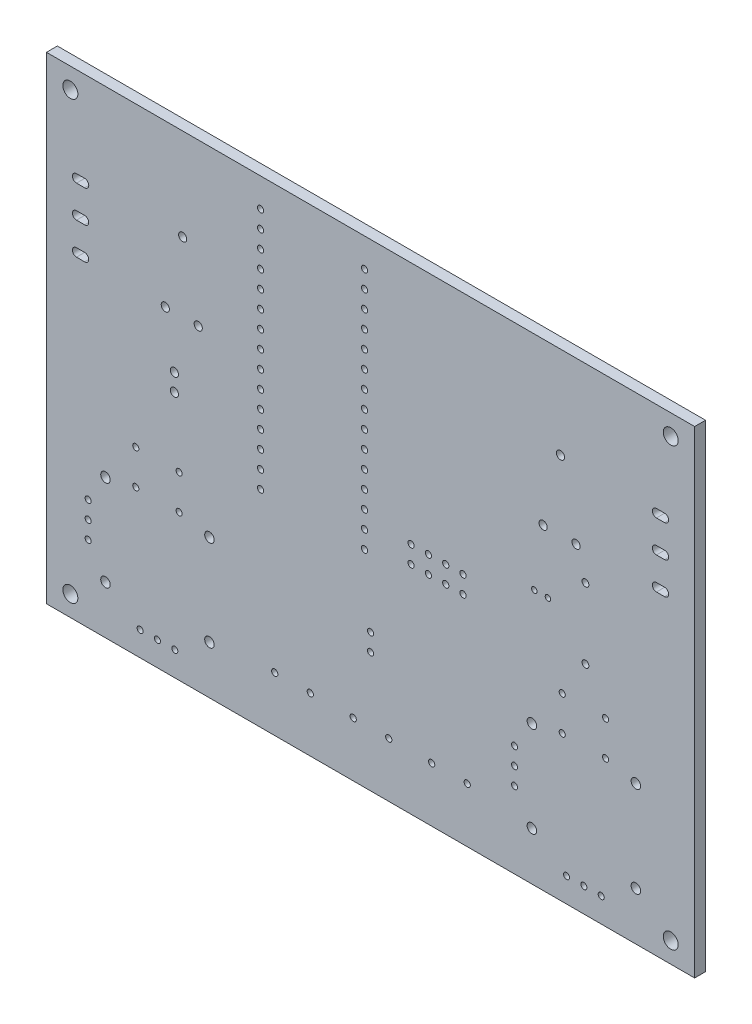
SolidWorks part; units mm, degrees
material "Copper"
ref_plane "Front" through (0, 0, 0) normal (0, 0, 1) x (1, 0, 0)
ref_plane "Top" through (0, 0, 0) normal (0, 1, 0) x (1, 0, 0)
ref_plane "Right" through (0, 0, 0) normal (1, 0, 0) x (0, 0, -1)
sketch "Sketch1" plane through (0, 0, 0) normal (0, 0, 1) x (1, 0, 0)
  line B0 (0, 70) -> (0, 0)
  circle B1 centre (19.9601, 56.5399) radius 1.08
  circle B2 centre (31.38, 60.7) radius 0.4572
  circle B3 centre (31.3799, 60.6999) radius 0.762
  circle B4 centre (31.38, 58.16) radius 0.4572
  circle B5 centre (17.42, 46.38) radius 0.6
  circle B6 centre (17.4201, 46.3799) radius 1.08
  line B7 (95, 70) -> (0, 70)
  line B8 (0, 0) -> (95, 0)
  line B9 (95, 0) -> (95, 70)
  line B10 (6, 57.2) -> (4, 57.2)
  line B11 (4, 57.2) -> (6, 57.2)
  line B12 (6, 55.2) -> (4, 55.2)
  line B13 (4, 55.2) -> (6, 55.2)
  line B14 (5.6, 56.8) -> (4.4, 56.8)
  line B15 (4.4, 56.8) -> (5.6, 56.8)
  line B16 (5.6, 55.6) -> (4.4, 55.6)
  line B17 (4.4, 55.6) -> (5.6, 55.6)
  line B18 (6, 52.5) -> (4, 52.5)
  line B19 (4, 52.5) -> (6, 52.5)
  line B20 (6, 50.5) -> (4, 50.5)
  line B21 (4, 50.5) -> (6, 50.5)
  line B22 (5.6, 52.1) -> (4.4, 52.1)
  line B23 (4.4, 52.1) -> (5.6, 52.1)
  line B24 (5.6, 50.9) -> (4.4, 50.9)
  line B25 (4.4, 50.9) -> (5.6, 50.9)
  line B26 (6, 47.8) -> (4, 47.8)
  line B27 (4, 47.8) -> (6, 47.8)
  line B28 (6, 45.8) -> (4, 45.8)
  line B29 (4, 45.8) -> (6, 45.8)
  line B30 (5.6, 47.4) -> (4.4, 47.4)
  line B31 (4.4, 47.4) -> (5.6, 47.4)
  line B32 (5.6, 46.2) -> (4.4, 46.2)
  line B33 (4.4, 46.2) -> (5.6, 46.2)
  line B34 (91.0001, 57.2) -> (89.0001, 57.2)
  line B35 (89.0001, 57.2) -> (91.0001, 57.2)
  line B36 (91.0001, 55.2) -> (89.0001, 55.2)
  line B37 (89.0001, 55.2) -> (91.0001, 55.2)
  line B38 (90.6, 56.8) -> (89.4, 56.8)
  line B39 (89.4, 56.8) -> (90.6, 56.8)
  line B40 (90.6, 55.6) -> (89.4, 55.6)
  line B41 (89.4, 55.6) -> (90.6, 55.6)
  line B42 (91.0001, 52.5) -> (89.0001, 52.5)
  line B43 (89.0001, 52.5) -> (91.0001, 52.5)
  line B44 (91.0001, 50.5) -> (89.0001, 50.5)
  line B45 (89.0001, 50.5) -> (91.0001, 50.5)
  line B46 (90.6, 52.1) -> (89.4, 52.1)
  line B47 (89.4, 52.1) -> (90.6, 52.1)
  line B48 (90.6, 50.9) -> (89.4, 50.9)
  line B49 (89.4, 50.9) -> (90.6, 50.9)
  line B50 (91.0001, 47.8) -> (89.0001, 47.8)
  line B51 (89.0001, 47.8) -> (91.0001, 47.8)
  line B52 (91.0001, 45.8) -> (89.0001, 45.8)
  line B53 (89.0001, 45.8) -> (91.0001, 45.8)
  line B54 (90.6, 47.4) -> (89.4, 47.4)
  line B55 (89.4, 47.4) -> (90.6, 47.4)
  line B56 (90.6, 46.2) -> (89.4, 46.2)
  line B57 (89.4, 46.2) -> (90.6, 46.2)
  line B58 (19.65, 39.67) -> (19.65, 37.87)
  line B59 (19.65, 37.87) -> (17.85, 37.87)
  line B60 (17.85, 37.87) -> (17.85, 39.67)
  line B61 (17.85, 39.67) -> (19.65, 39.67)
  line B62 (52.6907, 32.4793) -> (54.1893, 32.4793)
  line B63 (54.1893, 32.4793) -> (54.1893, 30.9807)
  line B64 (54.1893, 30.9807) -> (52.6907, 30.9807)
  line B65 (52.6907, 30.9807) -> (52.6907, 32.4793)
  circle B66 centre (19.96, 56.54) radius 0.6
  circle B67 centre (22.246, 46.38) radius 0.6
  circle B68 centre (22.2461, 46.3799) radius 1.08
  circle B69 centre (79.0004, 42.1504) radius 0.5
  circle B70 centre (79.0004, 42.1505) radius 0.762
  circle B71 centre (79.0004, 31.8504) radius 0.5
  circle B72 centre (79.0004, 31.8503) radius 0.762
  circle B73 centre (72.795, 46.38) radius 0.6
  circle B74 centre (72.7951, 46.3799) radius 1.08
  circle B75 centre (75.335, 56.54) radius 0.6
  circle B76 centre (75.3351, 56.5399) radius 1.08
  circle B77 centre (77.621, 46.38) radius 0.6
  circle B78 centre (77.6211, 46.3799) radius 1.08
  circle B79 centre (47.498, 20.143) radius 0.45
  circle B80 centre (47.498, 20.1429) radius 0.8255
  circle B81 centre (47.498, 17.603) radius 0.45
  circle B82 centre (47.498, 17.6029) radius 0.8255
  circle B83 centre (18.75, 36.23) radius 0.6
  circle B84 centre (18.75, 36.23) radius 0.9
  circle B85 centre (33.46, 8) radius 0.4572
  circle B86 centre (33.4599, 8) radius 1
  circle B87 centre (38.667, 8) radius 0.4572
  circle B88 centre (38.6669, 8) radius 1
  circle B89 centre (44.96, 8) radius 0.4572
  circle B90 centre (44.96, 8) radius 1
  circle B91 centre (50.167, 8) radius 0.4572
  circle B92 centre (50.167, 8) radius 1
  circle B93 centre (56.46, 8) radius 0.4572
  circle B94 centre (56.4601, 8) radius 1
  circle B95 centre (61.667, 8) radius 0.4572
  circle B96 centre (61.6671, 8) radius 1
  circle B97 centre (71.5, 37.5) radius 0.4
  circle B98 centre (71.5, 37.5) radius 0.65
  circle B99 centre (73.5, 37.5) radius 0.4
  circle B100 centre (73.5, 37.5) radius 0.65
  circle B101 centre (46.62, 30.22) radius 0.4572
  circle B102 centre (46.6199, 30.2199) radius 0.762
  circle B103 centre (46.62, 32.76) radius 0.4572
  circle B104 centre (46.6199, 32.7599) radius 0.762
  circle B105 centre (46.62, 35.3) radius 0.4572
  circle B106 centre (46.6199, 35.2999) radius 0.762
  circle B107 centre (46.62, 37.84) radius 0.4572
  circle B108 centre (46.6199, 37.8399) radius 0.762
  circle B109 centre (46.62, 40.38) radius 0.4572
  circle B110 centre (46.6199, 40.3799) radius 0.762
  circle B111 centre (46.62, 42.92) radius 0.4572
  circle B112 centre (46.6199, 42.9199) radius 0.762
  circle B113 centre (46.62, 45.46) radius 0.4572
  circle B114 centre (46.6199, 45.4599) radius 0.762
  circle B115 centre (46.62, 48) radius 0.4572
  circle B116 centre (46.6199, 47.9999) radius 0.762
  circle B117 centre (46.62, 50.54) radius 0.4572
  circle B118 centre (46.6199, 50.5399) radius 0.762
  circle B119 centre (46.62, 53.08) radius 0.4572
  circle B120 centre (46.6199, 53.0799) radius 0.762
  circle B121 centre (46.62, 55.62) radius 0.4572
  circle B122 centre (46.6199, 55.6199) radius 0.762
  circle B123 centre (46.62, 58.16) radius 0.4572
  circle B124 centre (46.6199, 58.1599) radius 0.762
  circle B125 centre (46.62, 60.7) radius 0.4572
  circle B126 centre (46.6199, 60.6999) radius 0.762
  circle B127 centre (46.62, 63.24) radius 0.4572
  circle B128 centre (46.6199, 63.2399) radius 0.762
  circle B129 centre (46.62, 65.78) radius 0.4572
  circle B130 centre (46.6199, 65.7799) radius 0.762
  circle B131 centre (31.38, 65.78) radius 0.4572
  circle B132 centre (31.3799, 65.7799) radius 0.762
  circle B133 centre (31.38, 63.24) radius 0.4572
  circle B134 centre (31.3799, 63.2399) radius 0.762
  circle B135 centre (31.3799, 58.1599) radius 0.762
  circle B136 centre (31.38, 55.62) radius 0.4572
  circle B137 centre (31.3799, 55.6199) radius 0.762
  circle B138 centre (31.38, 53.08) radius 0.4572
  circle B139 centre (31.3799, 53.0799) radius 0.762
  circle B140 centre (31.38, 50.54) radius 0.4572
  circle B141 centre (31.3799, 50.5399) radius 0.762
  circle B142 centre (31.38, 48) radius 0.4572
  circle B143 centre (31.3799, 47.9999) radius 0.762
  circle B144 centre (31.38, 45.46) radius 0.4572
  circle B145 centre (31.3799, 45.4599) radius 0.762
  circle B146 centre (31.38, 42.92) radius 0.4572
  circle B147 centre (31.3799, 42.9199) radius 0.762
  circle B148 centre (31.38, 40.38) radius 0.4572
  circle B149 centre (31.3799, 40.3799) radius 0.762
  circle B150 centre (31.38, 37.84) radius 0.4572
  circle B151 centre (31.3799, 37.8399) radius 0.762
  circle B152 centre (31.38, 35.3) radius 0.4572
  circle B153 centre (31.3799, 35.2999) radius 0.762
  circle B154 centre (31.38, 32.76) radius 0.4572
  circle B155 centre (31.3799, 32.7599) radius 0.762
  circle B156 centre (31.38, 30.22) radius 0.4572
  circle B157 centre (31.3799, 30.2199) radius 0.762
  circle B158 centre (8.65, 20.3848) radius 0.6985
  circle B159 centre (8.65, 20.3847) radius 1.143
  circle B160 centre (23.89, 20.3848) radius 0.6985
  circle B161 centre (23.89, 20.3847) radius 1.143
  circle B162 centre (23.89, 7.0752) radius 0.6985
  circle B163 centre (23.89, 7.0751) radius 1.143
  circle B164 centre (8.65, 7.0752) radius 0.6985
  circle B165 centre (8.65, 7.0751) radius 1.143
  circle B166 centre (18.81, 3.57) radius 0.4445
  circle B167 centre (18.81, 3.5699) radius 0.889
  circle B168 centre (16.27, 3.57) radius 0.4445
  circle B169 centre (16.27, 3.5699) radius 0.889
  circle B170 centre (13.73, 3.57) radius 0.4445
  circle B171 centre (13.73, 3.5699) radius 0.889
  circle B172 centre (6.11, 13.73) radius 0.4445
  circle B173 centre (6.11, 13.7299) radius 0.889
  circle B174 centre (6.11, 11.19) radius 0.4445
  circle B175 centre (6.11, 11.1899) radius 0.889
  circle B176 centre (6.11, 16.27) radius 0.4445
  circle B177 centre (6.11, 16.2699) radius 0.889
  circle B178 centre (19.445, 21.35) radius 0.4496
  circle B179 centre (19.445, 21.3499) radius 0.889
  circle B180 centre (13.095, 21.35) radius 0.4496
  circle B181 centre (13.095, 21.3499) radius 0.889
  circle B182 centre (13.095, 26.43) radius 0.4496
  circle B183 centre (13.095, 26.4299) radius 0.889
  circle B184 centre (19.445, 26.43) radius 0.4496
  circle B185 centre (19.445, 26.4299) radius 0.889
  circle B186 centre (71.15, 20.3848) radius 0.6985
  circle B187 centre (71.15, 20.3847) radius 1.143
  circle B188 centre (86.39, 20.3848) radius 0.6985
  circle B189 centre (86.39, 20.3847) radius 1.143
  circle B190 centre (86.39, 7.0752) radius 0.6985
  circle B191 centre (86.39, 7.0751) radius 1.143
  circle B192 centre (71.15, 7.0752) radius 0.6985
  circle B193 centre (71.15, 7.0751) radius 1.143
  circle B194 centre (81.31, 3.57) radius 0.4445
  circle B195 centre (81.31, 3.5699) radius 0.889
  circle B196 centre (78.77, 3.57) radius 0.4445
  circle B197 centre (78.77, 3.5699) radius 0.889
  circle B198 centre (76.23, 3.57) radius 0.4445
  circle B199 centre (76.23, 3.5699) radius 0.889
  circle B200 centre (68.61, 13.73) radius 0.4445
  circle B201 centre (68.61, 13.7299) radius 0.889
  circle B202 centre (68.61, 11.19) radius 0.4445
  circle B203 centre (68.61, 11.1899) radius 0.889
  circle B204 centre (68.61, 16.27) radius 0.4445
  circle B205 centre (68.61, 16.2699) radius 0.889
  circle B206 centre (81.945, 21.35) radius 0.4496
  circle B207 centre (81.945, 21.3499) radius 0.889
  circle B208 centre (75.595, 21.35) radius 0.4496
  circle B209 centre (75.595, 21.3499) radius 0.889
  circle B210 centre (75.595, 26.43) radius 0.4496
  circle B211 centre (75.595, 26.4299) radius 0.889
  circle B212 centre (81.945, 26.43) radius 0.4496
  circle B213 centre (81.945, 26.4299) radius 0.889
  circle B214 centre (55.98, 31.73) radius 0.4572
  circle B215 centre (55.9801, 31.7299) radius 0.7493
  circle B216 centre (58.52, 31.73) radius 0.4572
  circle B217 centre (58.5201, 31.7299) radius 0.7493
  circle B218 centre (61.06, 31.73) radius 0.4572
  circle B219 centre (61.0601, 31.7299) radius 0.7493
  circle B220 centre (61.06, 34.27) radius 0.4572
  circle B221 centre (61.0601, 34.2699) radius 0.7493
  circle B222 centre (58.52, 34.27) radius 0.4572
  circle B223 centre (58.5201, 34.2699) radius 0.7493
  circle B224 centre (55.98, 34.27) radius 0.4572
  circle B225 centre (55.9801, 34.2699) radius 0.7493
  circle B226 centre (53.44, 34.27) radius 0.4572
  circle B227 centre (53.4401, 34.2699) radius 0.7493
  arc B228 (4, 57.2) -> (4, 55.2) centre (4, 56.2) ccw
  arc B229 (6, 55.2) -> (6, 57.2) centre (6, 56.2) ccw
  arc B230 (4.4, 56.8) -> (4.4, 55.6) centre (4.4, 56.2) ccw
  arc B231 (5.6, 55.6) -> (5.6, 56.8) centre (5.6, 56.2) ccw
  arc B232 (4, 52.5) -> (4, 50.5) centre (4, 51.5) ccw
  arc B233 (6, 50.5) -> (6, 52.5) centre (6, 51.5) ccw
  arc B234 (4.4, 52.1) -> (4.4, 50.9) centre (4.4, 51.5) ccw
  arc B235 (5.6, 50.9) -> (5.6, 52.1) centre (5.6, 51.5) ccw
  arc B236 (4, 47.8) -> (4, 45.8) centre (4, 46.8) ccw
  arc B237 (6, 45.8) -> (6, 47.8) centre (6, 46.8) ccw
  arc B238 (4.4, 47.4) -> (4.4, 46.2) centre (4.4, 46.8) ccw
  arc B239 (5.6, 46.2) -> (5.6, 47.4) centre (5.6, 46.8) ccw
  arc B240 (89.0001, 57.2) -> (89.0001, 55.2) centre (89.0001, 56.2) ccw
  arc B241 (91.0001, 55.2) -> (91.0001, 57.2) centre (91.0001, 56.2) ccw
  arc B242 (89.4, 56.8) -> (89.4, 55.6) centre (89.4, 56.2) ccw
  arc B243 (90.6, 55.6) -> (90.6, 56.8) centre (90.6, 56.2) ccw
  arc B244 (89.0001, 52.5) -> (89.0001, 50.5) centre (89.0001, 51.5) ccw
  arc B245 (91.0001, 50.5) -> (91.0001, 52.5) centre (91.0001, 51.5) ccw
  arc B246 (89.4, 52.1) -> (89.4, 50.9) centre (89.4, 51.5) ccw
  arc B247 (90.6, 50.9) -> (90.6, 52.1) centre (90.6, 51.5) ccw
  arc B248 (89.0001, 47.8) -> (89.0001, 45.8) centre (89.0001, 46.8) ccw
  arc B249 (91.0001, 45.8) -> (91.0001, 47.8) centre (91.0001, 46.8) ccw
  arc B250 (89.4, 47.4) -> (89.4, 46.2) centre (89.4, 46.8) ccw
  arc B251 (90.6, 46.2) -> (90.6, 47.4) centre (90.6, 46.8) ccw
  circle B252 centre (18.75, 38.77) radius 0.6
  circle B253 centre (53.44, 31.73) radius 0.4572
  circle B254 centre (3.5001, 3) radius 1.1
  circle B255 centre (91.4999, 3) radius 1.1
  circle B256 centre (91.4999, 66.9998) radius 1.1
  circle B257 centre (3.5001, 66.9998) radius 1.1
sketch_block_instance "based-1"
sketch_block "based"
extrude "Boss-Extrude1" add sketch "Sketch1" along normal mid plane 1.6 contours B9 B7 B0 B8 B257 B256 B255 B254 B249 B52 B248 B50 B245 B44 B244 B42 B241 B36 B240 B34 B237 B28 B236 B26 B233 B20 B232 B18 B229 B12 B228 B10 B227 B225 B223 B221 | B12 B229 B10 B228 B231 B16 B230 B14 | B20 B233 B18 B232 B235 B24 B234 B22 | B28 B237 B26 B236 B239 B32 B238 B30 | B1 B66 | B6 B5 | B68 B67 | B61 B60 B59 B58 B252 | B84 B83 | B183 B182 | B185 B184 | B179 B178 | B181 B180 | B159 B158 | B161 B160 | B173 B172 | B175 B174 | B177 B176 | B165 B164 | B171 B170 | B169 B168 | B167 B166 | B163 B162 | B86 B85 | B88 B87 | B90 B89 | B92 B91 | B96 B95 | B94 B93 | B193 B192 | B203 B202 | B201 B200 | B205 B204 | B199 B198 | B197 B196 | B195 B194 | B191 B190 | B207 B206 | B189 B188 | B187 B186 | B209 B208 | B211 B210 | B213 B212 | B72 B71 | B100 B99 | B98 B97 | B78 B77 | B74 B73 | B70 B69 | B52 B249 B50 B248 B251 B56 B250 B54 | B44 B245 B42 B244 B247 B48 B246 B46 | B36 B241 B34 B240 B243 B40 B242 B38 | B76 B75 | B80 B79 | B82 B81 | B223 B222 | B217 B216 | B215 B214 | B219 B218 | B65 B64 B63 B62 B253 | B225 B224 | B227 B226 | B102 B101 | B104 B103 | B106 B105 | B108 B107 | B110 B109 | B112 B111 | B114 B113 | B116 B115 | B118 B117 | B122 B121 | B120 B119 | B124 B123 | B126 B125 | B128 B127 | B130 B129 | B132 B131 | B135 B4 | B3 B2 | B134 B133 | B137 B136 | B141 B140 | B139 B138 | B143 B142 | B145 B144 | B149 B148 | B147 B146 | B151 B150 | B153 B152 | B155 B154 | B157 B156 | B221 B220 region at (47.5716, 35.0845, 0) region at (18.9106, 56.5399, 0) region at (30.6395, 60.6999, 0) region at (16.3706, 46.3799, 0) region at (6.9553, 56.2, 0) region at (6.9553, 51.5, 0) region at (6.9553, 46.8, 0) region at (91.9553, 56.2, 0) region at (91.9553, 51.5, 0) region at (91.9553, 46.8, 0) region at (19.6245, 38.77, 0) region at (53.44, 32.4581, 0) region at (21.1966, 46.3799, 0) region at (78.2599, 42.1505, 0) region at (78.2599, 31.8503, 0) region at (71.7457, 46.3799, 0) region at (74.2857, 56.5399, 0) region at (76.5717, 46.3799, 0) region at (46.6958, 20.1429, 0) region at (46.6958, 17.6029, 0) region at (17.8755, 36.23, 0) region at (32.4882, 8, 0) region at (37.6952, 8, 0) region at (43.9883, 8, 0) region at (49.1953, 8, 0) region at (55.4884, 8, 0) region at (60.6954, 8, 0) region at (70.8684, 37.5, 0) region at (72.8684, 37.5, 0) region at (45.8795, 30.2199, 0) region at (45.8795, 32.7599, 0) region at (45.8795, 35.2999, 0) region at (45.8795, 37.8399, 0) region at (45.8795, 40.3799, 0) region at (45.8795, 42.9199, 0) region at (45.8795, 45.4599, 0) region at (45.8795, 47.9999, 0) region at (45.8795, 50.5399, 0) region at (45.8795, 53.0799, 0) region at (45.8795, 55.6199, 0) region at (45.8795, 58.1599, 0) region at (45.8795, 60.6999, 0) region at (45.8795, 63.2399, 0) region at (45.8795, 65.7799, 0) region at (30.6395, 65.7799, 0) region at (30.6395, 63.2399, 0) region at (30.6395, 58.1599, 0) region at (30.6395, 55.6199, 0) region at (30.6395, 53.0799, 0) region at (30.6395, 50.5399, 0) region at (30.6395, 47.9999, 0) region at (30.6395, 45.4599, 0) region at (30.6395, 42.9199, 0) region at (30.6395, 40.3799, 0) region at (30.6395, 37.8399, 0) region at (30.6395, 35.2999, 0) region at (30.6395, 32.7599, 0) region at (30.6395, 30.2199, 0) region at (7.5393, 20.3847, 0) region at (22.7793, 20.3847, 0)
